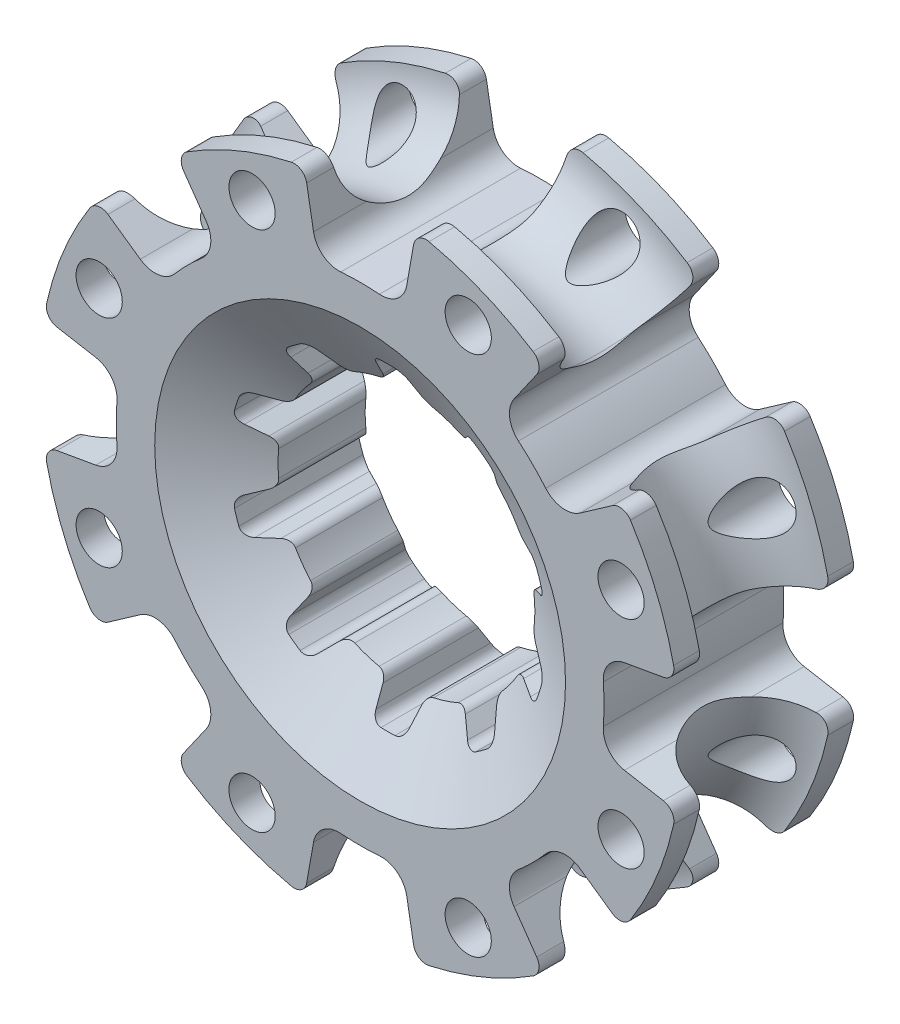
SolidWorks part; units mm, degrees
ref_plane "Front Plane" through (0, 0, 0) normal (0, 0, 1) x (1, 0, 0)
ref_plane "Top Plane" through (0, 0, 0) normal (0, 1, 0) x (1, 0, 0)
ref_plane "Right Plane" through (0, 0, 0) normal (1, 0, 0) x (0, 0, -1)
sketch "Sketch1" plane through (0, 0, 0) normal (0, 0, 1) x (1, 0, 0)
  circle A0 centre (0, 0) radius 125
  dimension "D1" = 250
extrude "Boss-Extrude1" add sketch "Sketch1" along normal blind 70
sketch "Sketch2" plane through (0, 0, 70) normal (0, 0, 1) x (1, 0, 0)
  line L0 (0, 78.7865) -> (0, -69.6432) construction
  line L1 (-20.8197, 118.0743) -> (-18.1502, 102.9348)
  line L2 (20.8197, 118.0743) -> (18.1502, 102.9348)
  circle A0 centre (0, 0) radius 110 construction
  arc A3 (7.5114, 94.7026) -> (-7.5114, 94.7026) centre (0, 0) ccw
  arc A6 (18.1502, 102.9348) -> (7.5114, 94.7026) centre (8.3021, 104.6713) cw
  arc A7 (-18.1502, 102.9348) -> (-7.5114, 94.7026) centre (-8.3021, 104.6713) ccw
  arc A10 (26.8164, 122.0896) -> (20.8197, 118.0743) centre (25.7437, 117.2061) ccw
  arc A11 (-26.8164, 122.0896) -> (-20.8197, 118.0743) centre (-25.7437, 117.2061) cw
  point P22 (0, 0)
  dimension "D2" = 220
  dimension "D3" = 190
  dimension "D4" = 20
  dimension "D5" = 5
  dimension "D6" = 10
  dimension "D7" = 5
extrude "Cut-Extrude2" cut sketch "Sketch2" against normal through all and the other way through all
pattern_circular "CirPattern1" count 8 over 360 about axis through (0, 0, 70) along (0, 0, 1) of "Cut-Extrude2"
sketch "Sketch3" plane through (0, 0, 70) normal (0, 0, 1) x (1, 0, 0)
  line L0 (-47.8354, 115.4849) -> (-37.3257, 90.1122) construction
  circle A0 centre (0, 0) radius 110 construction
  arc A1 (-26.8164, 122.0896) -> (-67.3684, 105.2925) centre (0, 0) ccw construction
  circle A2 centre (-42.0952, 101.6267) radius 9
  dimension "D1" = 220
  dimension "D2" = 18
extrude "Cut-Extrude3" cut sketch "Sketch3" against normal through all
pattern_circular "CirPattern2" count 8 over 360 about axis through (0, 0, 70) along (0, 0, 1) of "Cut-Extrude3"
sketch "Sketch4" plane through (0, 0, 0) normal (0.8192, -0.5736, 0) x (0, 0, -1)
  line L0 (0, 0) -> (-70, 0) construction
  line L1 (-35, 0) -> (-35, 124.8958) construction
  line L2 (0, 124.8958) -> (-70, 124.8958) construction
  circle A1 centre (-35, 124.8958) radius 25
  dimension "D1" = 50
ref_plane "Plane1" through (0, 0, 35) normal (0, 0, 1) x (1, 0, 0)
sketch "Sketch5" plane through (0, 0, 35) normal (0, 0, 1) x (1, 0, 0)
  circle A0 centre (0, 0) radius 110
  dimension "D1" = 220
sweep "Cut-Sweep2" cut profiles "Sketch4" path "Sketch5"
sketch "Sketch6" plane through (0, 0, 0) normal (0, 0, -1) x (-1, 0, 0)
  circle A0 centre (0, 0) radius 50
  dimension "D1" = 100
extrude "Cut-Extrude5" cut sketch "Sketch6" against normal through all
sketch "Sketch7" plane through (0, 0, 0) normal (0, 0, -1) x (-1, 0, 0)
  line L0 (0, 136.1682) -> (0, -134.9275) construction
  line L1 (-137.0987, 0) -> (137.0987, 0) construction
  line L2 (-6.4972, 58.5698) -> (-7.5151, 52.1429)
  line L3 (6.4972, 58.5698) -> (7.5151, 52.1429)
  circle A1 centre (0, 0) radius 50 construction
  arc A3 (2.7221, 61.9402) -> (-2.7221, 61.9402) centre (0, 0) ccw
  arc A4 (-18.1139, 46.6035) -> (17.6232, 46.7913) centre (0, 0) cw
  arc A5 (6.4972, 58.5698) -> (2.7221, 61.9402) centre (2.5464, 57.9441) ccw
  arc A6 (-6.4972, 58.5698) -> (-2.7221, 61.9402) centre (-2.5464, 57.9441) cw
  arc A7 (-10.6165, 48.8599) -> (-18.1139, 46.6035) centre (0, 0) ccw
  arc A8 (10.6165, 48.8599) -> (17.6232, 46.7913) centre (0, 0) cw
  arc A9 (10.6165, 48.8599) -> (7.5151, 52.1429) centre (11.4659, 52.7687) cw
  arc A10 (-10.6165, 48.8599) -> (-7.5151, 52.1429) centre (-11.4659, 52.7687) ccw
  point P18 (6, 61.709)
  point P21 (-6, 61.709)
  dimension "D4" = 4
  dimension "D5" = 4
  dimension "D2" = 18
  dimension "D3" = 12
extrude "Cut-Extrude6" cut sketch "Sketch7" against normal through all contours A10 A4 A9 L3 A5 A3 A6 L2 region at (0, 55.3354, 0)
pattern_circular "CirPattern3" count 10 over 360 about axis through (0, 0, 0) along (0, 0, -1) of "Cut-Extrude6"
sketch "Sketch8" plane through (0, 0, 0) normal (0, 0, -1) x (-1, 0, 0)
  circle A0 centre (0, 0) radius 80
  dimension "D1" = 160
extrude "Cut-Extrude7" cut sketch "Sketch8" against normal blind 70 draft 59
sketch "Sketch9" plane through (0, 0, 70) normal (0, 0, 1) x (1, 0, 0)
  circle A0 centre (0, 0) radius 80
  dimension "D1" = 160
extrude "Cut-Extrude8" cut sketch "Sketch9" against normal blind 70 draft 59
